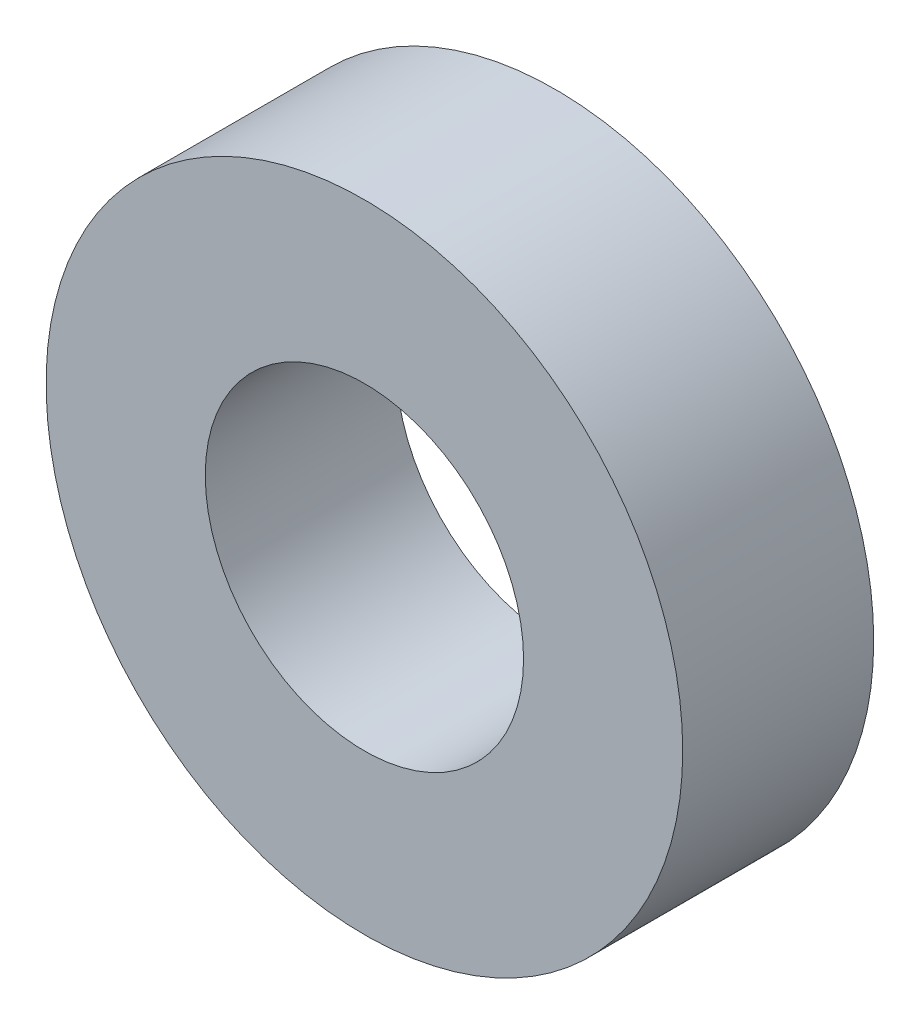
SolidWorks part; units mm, degrees
material "1100-H12 Rod (SS)"
ref_plane "Front Plane" through (0, 0, 0) normal (0, 0, 1) x (1, 0, 0)
ref_plane "Top Plane" through (0, 0, 0) normal (0, 1, 0) x (1, 0, 0)
ref_plane "Right Plane" through (0, 0, 0) normal (1, 0, 0) x (0, 0, -1)
ref_axis "Centre Axis" through (0, 0, -88.99) along (0, 0, 1)
sketch "Sketch1" plane through (0, 0, 0) normal (0, 0, 1) x (1, 0, 0)
  circle A0 centre (0, 0) radius 5
  circle A1 centre (0, 0) radius 2.5
  point P2 (0, 0)
  dimension "D1" = 5
  dimension "D2" = 10
extrude "Boss-Extrude1" add sketch "Sketch1" along normal blind 3
